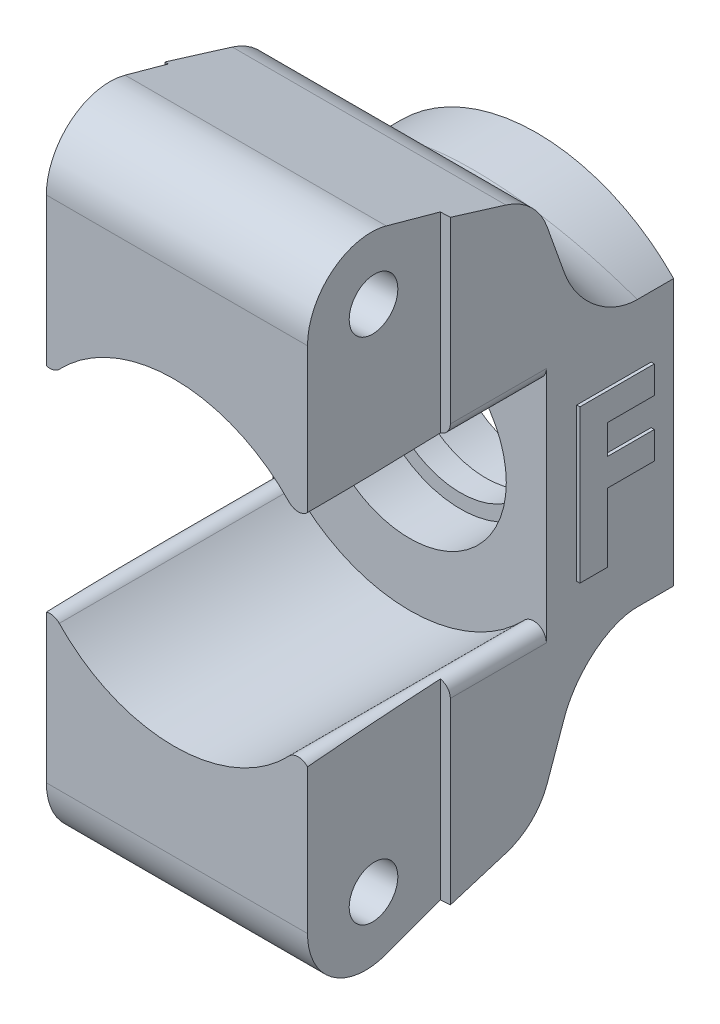
SolidWorks part; units mm, degrees
material "ABS"
ref_plane "Front Plane" through (0, 0, 0) normal (0, 0, 1) x (1, 0, 0)
ref_plane "Top Plane" through (0, 0, 0) normal (0, 1, 0) x (1, 0, 0)
ref_plane "Right Plane" through (0, 0, 0) normal (1, 0, 0) x (0, 0, -1)
sketch "Sketch1" plane through (0, 0, 0) normal (0, 0, 1) x (1, 0, 0)
  line L1 (-10.75, 18) -> (10.75, 18)
  line L2 (-10.75, 18) -> (-10.75, -18)
  line L3 (-10.75, -18) -> (10.75, -18)
  line L4 (10.75, 18) -> (10.75, -18)
  line L5 (-10.75, 18) -> (10.75, -18) construction
  line L6 (-10.75, -18) -> (10.75, 18) construction
  circle A0 centre (0, 0) radius 7.6
  point P0 (0, 0)
  dimension "D3" = 15.2
  dimension "D1" = 36
  dimension "D2" = 21.5
extrude "Boss-Extrude1" add sketch "Sketch1" along normal blind 4
sketch "Sketch2" plane through (0, 0, 4) normal (0, 0, 1) x (1, 0, 0)
  circle A0 centre (0, 0) radius 6.5
  line M1 (10.75, -18) -> (10.75, 18)
  line M2 (10.75, 18) -> (-10.75, 18)
  line M3 (-10.75, 18) -> (-10.75, -18)
  line M4 (-10.75, -18) -> (10.75, -18)
  circle M5 centre (0, 0) radius 7.6
  dimension "D1" = 13
extrude "Boss-Extrude2" add sketch "Sketch2" along normal blind 2 contours M4 M1 M2 M3 M5 | A0 M5 region at (0, -17.5807, 4) region at (-7.385, 0, 4)
sketch "Sketch3" plane through (0, 0, 6) normal (0, 0, 1) x (1, 0, 0)
  circle A0 centre (0, 0) radius 7.6
  circle A1 centre (0, 0) radius 7.6 construction
  line M1 (-10.75, -18) -> (10.75, -18)
  line M2 (10.75, -18) -> (10.75, 18)
  line M3 (10.75, 18) -> (-10.75, 18)
  line M4 (-10.75, 18) -> (-10.75, -18)
extrude "Boss-Extrude3" add sketch "Sketch3" along normal blind 4 contours A0 M4 M1 M2 M3 region at (-10.3307, 0, 6)
sketch "Sketch4" plane through (10.75, 0, 0) normal (1, 0, 0) x (0, 0, -1)
  line L0 (-23.5, 20) -> (-23.5, -20)
  line L2 (0, -18) -> (0, 18)
  line L4 (-10, -18) -> (-10, 18) construction
  line L5 (0, 18) -> (-22.0295, 24.7789)
  line L6 (-28.5, 20) -> (-28.5, -20)
  line L7 (0, -18) -> (-22.0295, -24.7789)
  line L8 (-23.5, 0) -> (0, 0) construction
  line L9 (0, 18) -> (-10, 18)
  line L10 (-10, 18) -> (-10, -18)
  line L11 (-10, -18) -> (0, -18)
  circle A0 centre (-23.5, 20) radius 2.1
  circle A1 centre (-23.5, 20) radius 5
  circle A2 centre (-23.5, -20) radius 2.1
  circle A3 centre (-23.5, -20) radius 5
  point P2 (0, 0)
  point P7 (-23.5, 0)
  line M3 (0, 18) -> (-10, 18)
  line M4 (-10, 18) -> (-10, -18)
  line M5 (-10, -18) -> (0, -18)
  dimension "D1" = 4.2
  dimension "D2" = 10
  dimension "D3" = 4.2
  dimension "D4" = 10
  dimension "D5" = 13.5
  dimension "D6" = 40
extrude "Boss-Extrude4" add sketch "Sketch4" against normal up to surface (21.5 mm away) contours L0 L8 L5 A1 M4 M3 | L8 L0 A3 L7 L10 M5 | A3 L0 A1 L6 | A1 A0 | A3 A2 | A0 | A2 region at (10.75, 16.5645, 26.9355) region at (10.75, 10.8564, 15.7987) region at (10.75, 0, 26.0923) region at (10.75, 21.4429, 24.9429) region at (10.75, -10.8564, 15.7987) region at (10.75, -18.5571, 22.0571) region at (10.75, -16.5645, 20.0645) up to face at (-10.75, 0, 5)
sketch "Sketch5" plane through (0, 0, 28.5) normal (0, 0, 1) x (1, 0, 0)
  circle A0 centre (0, 0) radius 12.5
  dimension "D1" = 25
extrude "Cut-Extrude1" cut sketch "Sketch5" against normal up to surface (18.5 mm away)
fillet "Fillet1" radius 1 4 edges at (-10.75, -6.3787, 19.25) (10.75, -6.3787, 19.25) (10.75, 6.3787, 19.25) (-10.75, 6.3787, 19.25)
sketch "Sketch6" plane through (0, 0, 0) normal (0, 0, -1) x (-1, 0, 0)
  line L1 (-35, 35) -> (35, 35)
  line L2 (-35, 35) -> (-35, -35)
  line L3 (-35, -35) -> (35, -35)
  line L4 (35, 35) -> (35, -35)
  line L5 (-35, 35) -> (35, -35) construction
  line L6 (-35, -35) -> (35, 35) construction
  circle A0 centre (0, 0) radius 15
  dimension "D1" = 30
  dimension "D2" = 70
  dimension "D3" = 70
extrude "Cut-Extrude2" cut sketch "Sketch6" against normal blind 6
chamfer "Chamfer1" distance 12 distance2 5 1 edges at (0, 19.8463, 6) first distance on face at (0, 16.2885, 6)
chamfer "Chamfer2" distance 5 distance2 12 1 edges at (0, -19.8463, 6) first distance on face at (0, -22.3126, 14.0147)
fillet "Fillet2" radius 5 4 edges at (0, -15, 8.5379) (0, -21.3168, 10.7789) (0, 15, 8.5379) (0, 21.3168, 10.7789)
sketch "Sketch7" plane through (0, 0, 0) normal (1, 0, 0) x (0, 0, -1)
  line L0 (-23.5, 20) -> (-23.5, -20) construction
  circle A0 centre (-23.5, 20) radius 1.6
  circle A1 centre (-23.5, -20) radius 1.6
  dimension "D4" = 3.2
  dimension "D5" = 3.2
  dimension "D1" = 23.5
  dimension "D2" = 20
  dimension "D3" = 40
ref_plane "Plane1" through (-1.0241, 0, 0.0447) normal (0.999, 0, -0.0436) x (0, -1, 0)
sketch "Sketch8" plane through (-1.0241, 0, 0.0447) normal (0.999, 0, -0.0436) x (0, -1, 0)
  line L1 (-30, -18) -> (30, -18)
  line L2 (-30, -18) -> (-30, -29)
  line L3 (-30, -29) -> (30, -29)
  line L4 (30, -18) -> (30, -29)
  line L5 (-30, -18) -> (30, -29) construction
  line L6 (-30, -29) -> (30, -18) construction
  circle A0 centre (-20, -23.5) radius 2
  circle A1 centre (20, -23.5) radius 2
  circle A2 centre (-20, -23.5) radius 5.5
  circle A3 centre (20, -23.5) radius 5.5
  point P5 (0, -23.5)
  dimension "D1" = 4
  dimension "D2" = 4
  dimension "D6" = 11
  dimension "D7" = 11
  dimension "D3" = 23.5
  dimension "D4" = 20
  dimension "D5" = 40
  dimension "D8" = 11
  dimension "D9" = 60
extrude "Cut-Extrude3" cut sketch "Sketch8" against normal through all both and the other way through all contours A1 | A0 region at (0.001, 20, 23.5223) region at (0.001, -20, 23.5223)
extrude "Cut-Extrude4" cut sketch "Sketch8<3>" along normal blind 0.75 from offset 10.25 contours L4 L3 L2 L1
sketch "Sketch8<3>" plane through (-1.0241, 0, 0.0447) normal (0.999, 0, -0.0436) x (0, -1, 0) same geometry as "Sketch8"
extrude "Cut-Extrude5" cut sketch "Sketch8<4>" against normal blind 0.75 from offset 10.25 contours L3 L4 L1 L2 offset against normal yes
sketch "Sketch8<4>" plane through (-1.0241, 0, 0.0447) normal (0.999, 0, -0.0436) x (0, -1, 0) same geometry as "Sketch8"
sketch "Sketch9" plane through (10.75, 0, 0) normal (1, 0, 0) x (0, 0, -1)
  line L0 (-10, -6.3374) -> (0, -6.3374) construction
  line L1 (-10, -9.3374) -> (-10, 9.3374) construction
  line L2 (0, -10.4612) -> (0, 10.4612) construction
  line L3 (-10, -9.3374) -> (-17.5478, -9.3374) construction
  text T0 "<b>F</b>" font "Century Gothic" height 12
  dimension "D1" = 3
sketch "Sketch10" plane through (-10.75, 0, 0) normal (-1, 0, 0) x (0, 0, 1)
  line L0 (0, -6.3374) -> (10, -6.3374) construction
  line L1 (0, 10.4612) -> (0, -10.4612) construction
  line L2 (10, 9.3374) -> (10, -9.3374) construction
  line L3 (18.4865, -9.3374) -> (10, -9.3374) construction
  text T0 "<b>B</b>" font "Century Gothic" height 12
  dimension "D1" = 3
extrude "Boss-Extrude5" add sketch "Sketch9" along normal blind 0.25
extrude "Boss-Extrude6" add sketch "Sketch10" along normal blind 0.25
equation "\"D3@Sketch4\"=\"D1@Sketch4\""
equation "\"D4@Sketch4\"=\"D2@Sketch4\""
equation "\"D5@Sketch7\"=\"D4@Sketch7\""
equation "\"D2@Sketch8\"=\"D1@Sketch8\""
